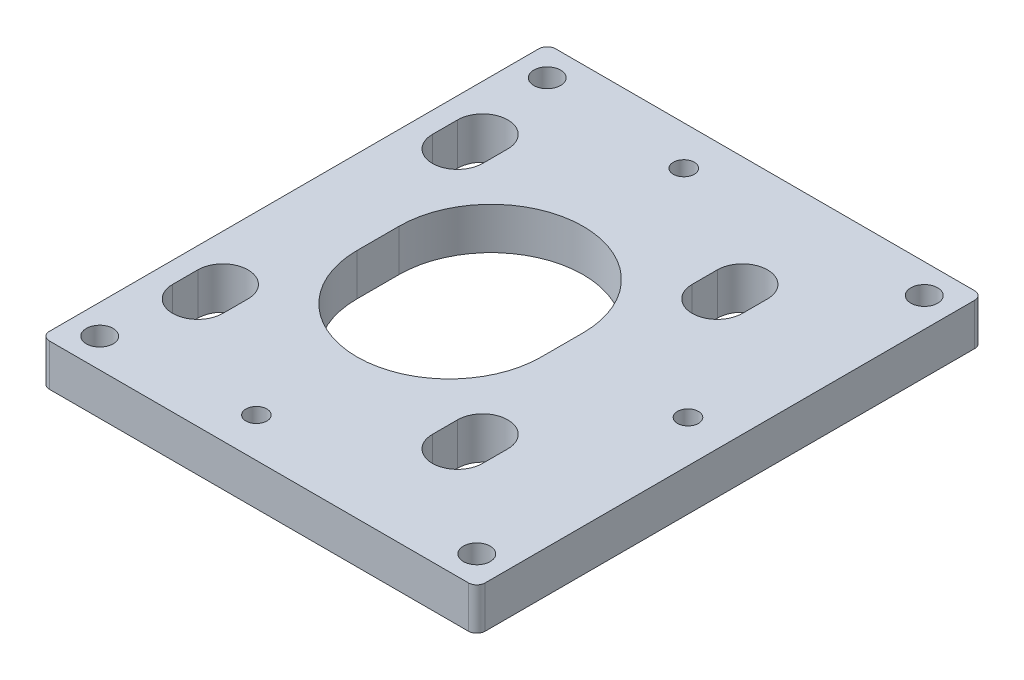
SolidWorks part; units mm, degrees
material "AISI 1045 Steel, cold drawn"
ref_plane "Front Plane" through (0, 0, 0) normal (0, 0, 1) x (1, 0, 0)
ref_plane "Top Plane" through (0, 0, 0) normal (0, 1, 0) x (1, 0, 0)
ref_plane "Right Plane" through (0, 0, 0) normal (1, 0, 0) x (0, 0, -1)
sketch "Sketch1" plane through (0, 0, 0) normal (0, 1, 0) x (1, 0, 0)
  line L0 (0, -2.5) -> (0, 2.5) construction
  line L1 (-11, -2.5) -> (-11, 2.5)
  line L2 (11, -2.5) -> (11, 2.5)
  line L3 (-15.5, 14) -> (-15.5, 17) construction
  line L4 (-18.5, 14) -> (-18.5, 17)
  line L5 (-12.5, 14) -> (-12.5, 17)
  line L6 (15.5, 14) -> (15.5, 17) construction
  line L7 (12.5, 14) -> (12.5, 17)
  line L8 (18.5, 14) -> (18.5, 17)
  line L9 (15.5, -17) -> (15.5, -14) construction
  line L10 (12.5, -17) -> (12.5, -14)
  line L11 (18.5, -17) -> (18.5, -14)
  line L12 (-15.5, -17) -> (-15.5, -14) construction
  line L13 (-18.5, -17) -> (-18.5, -14)
  line L14 (-12.5, -17) -> (-12.5, -14)
  line L15 (-15.5, 15.5) -> (15.5, 15.5) construction
  line L16 (-15.5, -15.5) -> (-15.5, 15.5) construction
  line L17 (21, -30.2) -> (21, 30.2) construction
  line L18 (-21, 30.2) -> (31, 30.2)
  line L19 (-21, 30.2) -> (-21, -30.2)
  line L20 (-21, -30.2) -> (31, -30.2)
  line L21 (31, 30.2) -> (31, -30.2)
  arc A0 (-11, -2.5) -> (11, -2.5) centre (0, -2.5) ccw
  arc A1 (11, 2.5) -> (-11, 2.5) centre (0, 2.5) ccw
  arc A2 (-18.5, 14) -> (-12.5, 14) centre (-15.5, 14) ccw
  arc A3 (-12.5, 17) -> (-18.5, 17) centre (-15.5, 17) ccw
  arc A4 (12.5, 14) -> (18.5, 14) centre (15.5, 14) ccw
  arc A5 (18.5, 17) -> (12.5, 17) centre (15.5, 17) ccw
  arc A6 (12.5, -17) -> (18.5, -17) centre (15.5, -17) ccw
  arc A7 (18.5, -14) -> (12.5, -14) centre (15.5, -14) ccw
  arc A8 (-18.5, -17) -> (-12.5, -17) centre (-15.5, -17) ccw
  arc A9 (-12.5, -14) -> (-18.5, -14) centre (-15.5, -14) ccw
  point P2 (0, 0)
  point P10 (-15.5, 15.5)
  point P16 (15.5, 15.5)
  point P23 (15.5, -15.5)
  point P30 (-15.5, -15.5)
  point P38 (0, 15.5)
  point P40 (-15.5, 0)
  point P43 (31, 0)
  dimension "D2" = 11
  dimension "D3" = 3
  dimension "D1" = 5
  dimension "D4" = 31
  dimension "D5" = 3
  dimension "D6" = 30.2
  dimension "D7" = 21
  dimension "D8" = 21
  dimension "D9" = 10
extrude "Boss-Extrude1" add sketch "Sketch1" along normal blind 5
hole_wizard "M3 Clearance Hole1" positions "Sketch2" profile "Sketch3" hole size "M3" standard "ANSI Metric" end condition through all
sketch "Sketch2" plane through (0, 5, 0) normal (0, 1, 0) x (1, 0, 0)
  line L0 (-21, -30.2) -> (31, -30.2) construction
  line L1 (-21, 30.2) -> (-21, -30.2) construction
  line L2 (31, -30.2) -> (31, 30.2) construction
  line L3 (31, 30.2) -> (-21, 30.2) construction
  point P0 (-17.5, -26.7)
  point P2 (27.5, -26.7)
  point P4 (27.5, 26.7)
  point P6 (-17.5, 26.7)
  dimension "D1" = 3.5
  dimension "D2" = 3.5
  dimension "D3" = 3.5
  dimension "D4" = 3.5
sketch "Sketch3" plane through (-17.5, 5, 26.7) normal (1, 0, 0) x (0, 0, 1)
  line L0 (0, 0) -> (0, 5)
  line L1 (0, 5) -> (1.6, 5)
  line L2 (1.6, 5) -> (1.6, 0)
  line L5 (1.6, 0) -> (0, 0)
  line L11 (0, -6.35) -> (0, 107.95) construction
  dimension "Thru Hole Dia." = 3.2
  dimension "Thru Hole Depth" = 5
fillet "Fillet1" radius 1 4 edges at (31, 2.5, -30.2) (-21, 2.5, -30.2) (31, 2.5, 30.2) (-21, 2.5, 30.2)
hole_wizard "Tap Drill for M3x0.5 Tap1" positions "Sketch4" profile "Sketch5" hole size "M3x0.5" standard "ANSI Metric" end condition through all
sketch "Sketch4" plane through (0, 5, 0) normal (0, 1, 0) x (1, 0, 0)
  point P0 (26, 0)
  point P6 (0, 25.5)
  point P8 (0, -25.5)
  point P14 (-0.1278, 18.4279)
  point P18 (0, 0)
  point P19 (0, 0)
  dimension "D1" = 26
  dimension "D2" = 25.5
  dimension "D3" = 25.5
sketch "Sketch5" plane through (26, 5, 0) normal (1, 0, 0) x (0, 0, 1)
  line L0 (0, 0) -> (0, 5)
  line L1 (0, 5) -> (1.25, 5)
  line L2 (1.25, 5) -> (1.25, 0)
  line L5 (1.25, 0) -> (0, 0)
  line L11 (0, -6.35) -> (0, 107.95) construction
  dimension "Thru Hole Dia." = 2.5
  dimension "Thru Hole Depth" = 5
